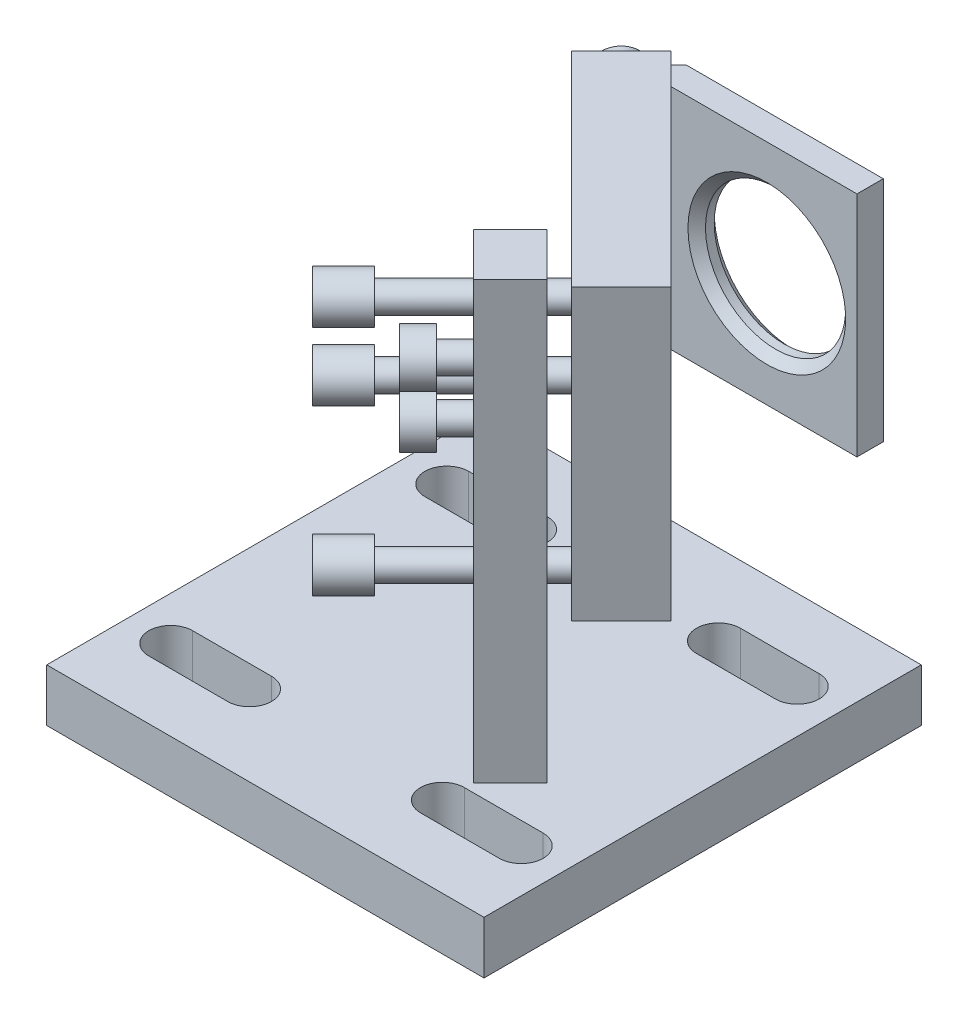
SolidWorks part; units mm, degrees
ref_plane "laser Y plane" through (0, 0, 0) normal (0, 0, 1) x (1, 0, 0)
ref_plane "laser Z plane" through (0, 0, 0) normal (0, 1, 0) x (1, 0, 0)
ref_plane "laser tube plane" through (0, 0, 0) normal (1, 0, 0) x (0, 0, -1)
ref_plane "Plane1" through (0, -32.5, 0) normal (0, 1, 0) x (1, 0, 0)
sketch "Sketch1" plane through (0, -32.5, 0) normal (0, 1, 0) x (1, 0, 0)
  line L0 (0, 0) -> (56.0742, 0) construction
  line L1 (0, 0) -> (0, 59.4556) construction
  line L2 (1.05, 5.8) -> (10.05, 5.8) construction
  line L3 (-34.9, 15) -> (15, 15)
  line L4 (-34.9, 15) -> (-34.9, -34.9)
  line L5 (-34.9, -34.9) -> (15, -34.9)
  line L6 (15, 15) -> (15, -34.9)
  line L7 (1.05, 8.3) -> (10.05, 8.3)
  line L8 (1.05, 3.3) -> (10.05, 3.3)
  line L9 (-9.95, 15) -> (-9.95, -34.9) construction
  line L10 (-34.9, -9.95) -> (15, -9.95) construction
  line L11 (-20.95, 5.8) -> (-29.95, 5.8) construction
  line L12 (-20.95, 8.3) -> (-29.95, 8.3)
  line L13 (-20.95, 3.3) -> (-29.95, 3.3)
  line L14 (-20.95, -25.7) -> (-29.95, -25.7) construction
  line L15 (-20.95, -28.2) -> (-29.95, -28.2)
  line L16 (-20.95, -23.2) -> (-29.95, -23.2)
  line L17 (1.05, -25.7) -> (10.05, -25.7) construction
  line L18 (1.05, -28.2) -> (10.05, -28.2)
  line L19 (1.05, -23.2) -> (10.05, -23.2)
  arc A0 (1.05, 8.3) -> (1.05, 3.3) centre (1.05, 5.8) ccw
  arc A1 (10.05, 3.3) -> (10.05, 8.3) centre (10.05, 5.8) ccw
  arc A2 (-20.95, 8.3) -> (-20.95, 3.3) centre (-20.95, 5.8) cw
  arc A3 (-29.95, 3.3) -> (-29.95, 8.3) centre (-29.95, 5.8) cw
  arc A4 (-20.95, -28.2) -> (-20.95, -23.2) centre (-20.95, -25.7) ccw
  arc A5 (-29.95, -23.2) -> (-29.95, -28.2) centre (-29.95, -25.7) ccw
  arc A6 (1.05, -28.2) -> (1.05, -23.2) centre (1.05, -25.7) cw
  arc A7 (10.05, -23.2) -> (10.05, -28.2) centre (10.05, -25.7) cw
  point P10 (5.55, 5.8)
  point P21 (-25.45, 5.8)
  point P28 (-25.45, -25.7)
  point P35 (5.55, -25.7)
  dimension "D7" = 22
  dimension "D1" = 49.9
  dimension "D2" = 49.9
  dimension "D3" = 15
  dimension "D4" = 15
  dimension "D5" = 5
  dimension "D6" = 9
  dimension "D8" = 26.5
  dimension "D9" = 6.7
  dimension "D10" = 31.5
  dimension "D11" = 31
extrude "Boss-Extrude1" add sketch "Sketch1" against normal blind 6
ref_axis "Axis1" through (0, 50, 0) along (0, -1, 0)
ref_plane "mirror plane" through (0, 0, 0) normal (0.7071, 0, -0.7071) x (0, -1, 0)
ref_axis "incoming laser beam" through (0, 0, -80.9) along (0, 0, 1)
ref_axis "outgoing laser beam" through (2.1578, 0, 0) along (1, 0, 0)
ref_plane "Plane3" through (-6.364, 0, 6.364) normal (0.7071, 0, -0.7071) x (0, -1, 0)
sketch "Sketch2" plane through (-6.364, 0, 6.364) normal (0.7071, 0, -0.7071) x (0, -1, 0)
  line L0 (-50, 0) -> (50, 0) construction
  line L1 (0, 50) -> (0, -50) construction
  line L2 (-5.5453, -9.5) -> (-17.25, -9.5)
  line L3 (-17.25, -9.5) -> (-17.25, -16.5)
  line L4 (-17.25, -16.5) -> (32.5, -16.5)
  line L5 (32.5, -16.5) -> (32.5, 16.5)
  line L6 (32.5, 16.5) -> (8.9, 16.5)
  line L7 (8.9, 16.5) -> (8.9, 6.4645)
  line L8 (32.5, 35.2846) -> (32.5, 0) construction
  line L9 (0, 0) -> (21.3656, 0) construction
  arc A0 (-5.5453, -9.5) -> (8.9, 6.4645) centre (0, 0) ccw
  dimension "D1" = 22
  dimension "D2" = 33
  dimension "D3" = 7
  dimension "D4" = 49.75
  dimension "D5" = 23.6
extrude "Boss-Extrude2" add sketch "Sketch2" against normal blind 5.9
sketch "Sketch3" plane through (-10.5359, 0, 10.5359) normal (-0.7071, 0, 0.7071) x (0.7071, 0, 0.7071)
  line L0 (0, 0) -> (37.2247, 0) construction
  line L1 (0, 0) -> (0, 17.5234) construction
  line L2 (13.25, 13.25) -> (13.25, -13.25) construction
  line L3 (13.25, -13.25) -> (-13.25, -13.25) construction
  arc A0 (-6.4645, -8.9) -> (9.5, 5.5453) centre (0, 0) ccw construction
  arc A1 (-6.4645, -8.9) -> (9.5, 5.5453) centre (0, 0) ccw construction
  circle A2 centre (13.25, 13.25) radius 1.5
  circle A3 centre (13.25, -13.25) radius 1.5
  circle A4 centre (-13.25, -13.25) radius 1.5
  point P7 (0, 0)
  point P11 (0, 0)
  point P13 (0, 0)
  point P14 (0, 0)
  point P15 (0, 0)
  dimension "D1" = 3
  dimension "D2" = 26.5
  dimension "D3" = 26.5
extrude "Boss-Extrude3" add sketch "Sketch3" along normal blind 13 and the other way up to surface (14.9 mm away) other way up to plane "mirror plane"
sketch "Sketch4" plane through (-19.7283, 0, 19.7283) normal (-0.7071, 0, 0.7071) x (0.7071, 0, 0.7071)
  circle A0 centre (13.25, 13.25) radius 2.5
  circle A1 centre (13.25, -13.25) radius 2.5
  circle A2 centre (-13.25, -13.25) radius 2.5
  dimension "D1" = 5
extrude "Boss-Extrude4" add sketch "Sketch4" against normal blind 5
sketch "Sketch5" plane through (-10.5359, 0, 10.5359) normal (-0.7071, 0, 0.7071) x (0.7071, 0, 0.7071)
  line L0 (13.25, 13.25) -> (13.25, -13.25) construction
  line L1 (13.25, -13.25) -> (-13.25, -13.25) construction
  circle A0 centre (-7.25, -13.25) radius 1.5
  circle A1 centre (13.25, 7.25) radius 1.5
  point P10 (0, 0)
  point P11 (0, 0)
  dimension "D1" = 3
  dimension "D2" = 6
  dimension "D3" = 6
extrude "Boss-Extrude5" add sketch "Sketch5" along normal blind 3
sketch "Sketch6" plane through (-12.6572, 0, 12.6572) normal (-0.7071, 0, 0.7071) x (0.7071, 0, 0.7071)
  circle A0 centre (13.25, 7.25) radius 2.75
  circle A1 centre (-7.25, -13.25) radius 2.75
  dimension "D1" = 5.5
extrude "Boss-Extrude6" add sketch "Sketch6" along normal blind 0.5
sketch "Sketch7" plane through (-13.0108, 0, 13.0108) normal (-0.7071, 0, 0.7071) x (0.7071, 0, 0.7071)
  line L1 (-6.2214, -12.2374) -> (-7.6126, -11.8529)
  line L2 (-7.6126, -11.8529) -> (-8.6412, -12.8655)
  line L3 (13.7871, 5.9103) -> (14.6788, 7.0453)
  line L4 (14.6788, 7.0453) -> (14.1417, 8.385)
  line L5 (14.1417, 8.385) -> (12.7129, 8.5897)
  line L6 (12.7129, 8.5897) -> (11.8212, 7.4547)
  line L7 (11.8212, 7.4547) -> (12.3583, 6.115)
  line L8 (12.3583, 6.115) -> (13.7871, 5.9103)
  line L9 (-8.6412, -12.8655) -> (-8.2786, -14.2626)
  line L10 (-8.2786, -14.2626) -> (-6.8874, -14.6471)
  line L11 (-6.8874, -14.6471) -> (-5.8588, -13.6345)
  line L12 (-5.8588, -13.6345) -> (-6.2214, -12.2374)
  circle A0 centre (-7.25, -13.25) radius 2.75 construction
  circle A1 centre (13.25, 7.25) radius 2.75 construction
  circle A2 centre (-7.25, -13.25) radius 2.75
  circle A3 centre (13.25, 7.25) radius 2.75
  circle A4 centre (13.25, 7.25) radius 1.25 construction
  circle A5 centre (-7.25, -13.25) radius 1.25 construction
  dimension "D1" = 2.5
extrude "Boss-Extrude7" add sketch "Sketch7" along normal blind 2.5
sketch "Sketch8" plane through (0, 0, 0) normal (0.7071, 0, -0.7071) x (0, -1, 0)
  line L0 (0, 0) -> (0, 38.3007) construction
  line L1 (0, 0) -> (-35.7157, 0) construction
  line L3 (16.5, 16.5) -> (-16.5, 16.5)
  line L4 (16.5, 16.5) -> (16.5, -16.5)
  line L5 (16.5, -16.5) -> (-16.5, -16.5)
  line L6 (-16.5, 16.5) -> (-16.5, -16.5)
  line L7 (16.5, 16.5) -> (-16.5, -16.5) construction
  line L8 (16.5, -16.5) -> (-16.5, 16.5) construction
  circle A0 centre (0, 0) radius 8.675
  dimension "D2" = 17.35
  dimension "D1" = 33
extrude "Boss-Extrude8" add sketch "Sketch8" along normal blind 1
sketch "Sketch9" plane through (0, 0, 0) normal (-0.7071, 0, 0.7071) x (0.7071, 0, 0.7071)
  line L4 (16.5, 16.5) -> (-16.5, 16.5)
  line L5 (-16.5, 16.5) -> (-16.5, -16.5)
  line L6 (-16.5, -16.5) -> (16.5, -16.5)
  line L7 (16.5, -16.5) -> (16.5, 16.5)
  line L8 (16.5, 16.5) -> (-16.5, 16.5)
  line L9 (-16.5, 16.5) -> (-16.5, -16.5)
  line L10 (-16.5, -16.5) -> (16.5, -16.5)
  line L11 (16.5, -16.5) -> (16.5, 16.5)
  circle A0 centre (0, 0) radius 10.15
  dimension "D2" = 20.3
  dimension "D1" = 0
extrude "Boss-Extrude9" add sketch "Sketch9" along normal blind 7
sketch "Sketch10" plane through (0, 0, 0) normal (-0.7071, 0, 0.7071) x (0.7071, 0, 0.7071)
  circle A0 centre (0, 0) radius 10
  dimension "D1" = 20
extrude "Boss-Extrude10" add sketch "Sketch10" along normal blind 2
sketch "Sketch11" plane through (-1.4142, 0, 1.4142) normal (-0.7071, 0, 0.7071) x (0.7071, 0, 0.7071)
  circle A0 centre (0, 0) radius 10.15 construction
  circle A1 centre (0, 0) radius 10.15
  circle A2 centre (0, 0) radius 6
  dimension "D1" = 12
extrude "Boss-Extrude11" add sketch "Sketch11" along normal blind 3
sketch "Sketch12" plane through (0, -38.5, 0) normal (0, -1, 0) x (1, 0, 0)
  line L0 (1.1314, 22.2032) -> (5.3033, 18.0312) construction
  line L1 (5.3033, 18.0312) -> (-18.0312, -5.3033) construction
  line L2 (-22.2032, -1.1314) -> (-19.699, -3.6355) construction
  line L3 (1.1314, 22.2032) -> (-22.2032, -1.1314) construction
  line L4 (1.1314, 22.2032) -> (5.3033, 18.0312) construction
  line L5 (5.3033, 18.0312) -> (-18.0312, -5.3033) construction
  line L6 (-22.2032, -1.1314) -> (-18.0312, -5.3033) construction
  line L7 (1.1314, 22.2032) -> (-22.2032, -1.1314) construction
  line L8 (-20.1172, -3.2173) -> (3.2173, 20.1172) construction
  line L9 (-10.5359, 10.5359) -> (-6.364, 6.364) construction
  circle A0 centre (-15.3442, 1.5556) radius 2
  circle A1 centre (-1.5556, 15.3442) radius 2
  point P13 (0, 0)
  dimension "D1" = 19.5
  dimension "D2" = 4
extrude "Cut-Extrude1" cut sketch "Sketch12" against normal blind 13
sketch "Sketch13" plane through (0, -38.5, 0) normal (0, -1, 0) x (1, 0, 0)
  circle A0 centre (-15.3442, 1.5556) radius 4
  circle A1 centre (-1.5556, 15.3442) radius 4
  dimension "D1" = 8
extrude "Cut-Extrude2" cut sketch "Sketch13" against normal blind 4
sketch "Sketch14" plane through (0, -34.5, 0) normal (0, -1, 0) x (1, 0, 0)
  circle A0 centre (-15.3442, 1.5556) radius 3.5
  circle A1 centre (-1.5556, 15.3442) radius 3.5
  dimension "D1" = 7
extrude "Boss-Extrude12" add sketch "Sketch14" along normal blind 1
sketch "Sketch15" plane through (0, -35.5, 0) normal (0, -1, 0) x (1, 0, 0)
  line L1 (-14.2979, 2.936) -> (-16.0165, 3.1519)
  line L2 (-16.0165, 3.1519) -> (-17.0628, 1.7716)
  line L3 (-17.0628, 1.7716) -> (-16.3905, 0.1753)
  line L4 (-16.3905, 0.1753) -> (-14.672, -0.0406)
  line L5 (-14.672, -0.0406) -> (-13.6257, 1.3397)
  line L6 (-13.6257, 1.3397) -> (-14.2979, 2.936)
  line L7 (-2.6654, 16.674) -> (-3.2622, 15.048)
  line L8 (-3.2622, 15.048) -> (-2.1524, 13.7182)
  line L9 (-2.1524, 13.7182) -> (-0.4458, 14.0144)
  line L10 (-0.4458, 14.0144) -> (0.1509, 15.6404)
  line L11 (0.1509, 15.6404) -> (-0.9589, 16.9702)
  line L12 (-0.9589, 16.9702) -> (-2.6654, 16.674)
  circle A0 centre (-1.5556, 15.3442) radius 3.5 construction
  circle A1 centre (-15.3442, 1.5556) radius 3.5 construction
  circle A2 centre (-1.5556, 15.3442) radius 3.5
  circle A3 centre (-15.3442, 1.5556) radius 3.5
  circle A4 centre (-15.3442, 1.5556) radius 1.5 construction
  circle A5 centre (-1.5556, 15.3442) radius 1.5 construction
  dimension "D1" = 3
extrude "Boss-Extrude13" add sketch "Sketch15" along normal blind 3
sketch "Sketch16" plane through (0, 0, 0) normal (0, 1, 0) x (1, 0, 0)
  line L0 (-10.9602, 12.3744) -> (-16.617, 6.7175) construction
  line L1 (-10.9602, 12.3744) -> (-16.2635, 7.0711)
  line L2 (-16.2635, 7.0711) -> (-18.3848, 9.1924)
  line L3 (-18.3848, 9.1924) -> (-12.2028, 15.3744)
  line L4 (-12.2028, 15.3744) -> (10.2898, 15.3744)
  line L5 (10.2898, 15.3744) -> (10.2898, 12.3744)
  line L6 (10.2898, 12.3744) -> (-10.9602, 12.3744)
  dimension "D1" = 7.5
  dimension "D2" = 3
  dimension "D3" = 3
  dimension "D4" = 21.25
extrude "Boss-Extrude14" add sketch "Sketch16" along normal mid plane 26
sketch "Sketch17" plane through (0, 0, -15.3744) normal (0, 0, -1) x (-1, 0, 0)
  line L0 (0, 0) -> (0, -20.2812) construction
  circle A0 centre (0, 0) radius 8
  dimension "D1" = 16
extrude "Cut-Extrude3" cut sketch "Sketch17" against normal blind 3
chamfer "Chamfer1" distance 1 angle 45 2 edges at (-8, 0, -12.3744) (-8, 0, -15.3744)
sketch "Sketch18" plane through (-13.7886, 0, -13.7886) normal (-0.7071, 0, -0.7071) x (-0.7071, 0, 0.7071)
  line L0 (-1, 16.5) -> (7, 16.5) construction
  line L1 (-1, 16.5) -> (7, 16.5) construction
  line L2 (3, 16.5) -> (3, -14.02) construction
  line L3 (-2.2426, 13) -> (-2.2426, -13) construction
  line L4 (-2.2426, 13) -> (-2.2426, -13) construction
  line L5 (-2.2426, 0) -> (5.8439, 0) construction
  circle A0 centre (3, 10) radius 2.75
  circle A1 centre (3, -10) radius 2.75
  point P13 (0, 0)
  dimension "D1" = 5.5
  dimension "D2" = 20
extrude "Boss-Extrude15" add sketch "Sketch18" along normal blind 0.5
sketch "Sketch19" plane through (-14.1421, 0, -14.1421) normal (-0.7071, 0, -0.7071) x (-0.7071, 0, 0.7071)
  line L1 (1.8482, 9.1301) -> (3.1775, 8.5676)
  line L2 (3.1775, 8.5676) -> (4.3292, 9.4375)
  line L3 (4.3292, 9.4375) -> (4.1518, 10.8699)
  line L4 (4.1518, 10.8699) -> (2.8225, 11.4324)
  line L5 (2.8225, 11.4324) -> (1.6708, 10.5625)
  line L6 (1.6708, 10.5625) -> (1.8482, 9.1301)
  line L7 (3.6669, -11.2801) -> (4.442, -10.0625)
  line L8 (4.442, -10.0625) -> (3.7751, -8.7824)
  line L9 (3.7751, -8.7824) -> (2.3331, -8.7199)
  line L10 (2.3331, -8.7199) -> (1.558, -9.9375)
  line L11 (1.558, -9.9375) -> (2.2249, -11.2176)
  line L12 (2.2249, -11.2176) -> (3.6669, -11.2801)
  circle A0 centre (3, -10) radius 2.75 construction
  circle A1 centre (3, 10) radius 2.75 construction
  circle A2 centre (3, -10) radius 2.75
  circle A3 centre (3, 10) radius 2.75
  circle A4 centre (3, 10) radius 1.25 construction
  circle A5 centre (3, -10) radius 1.25 construction
  dimension "D1" = 2.5
extrude "Boss-Extrude16" add sketch "Sketch19" along normal blind 2.5
